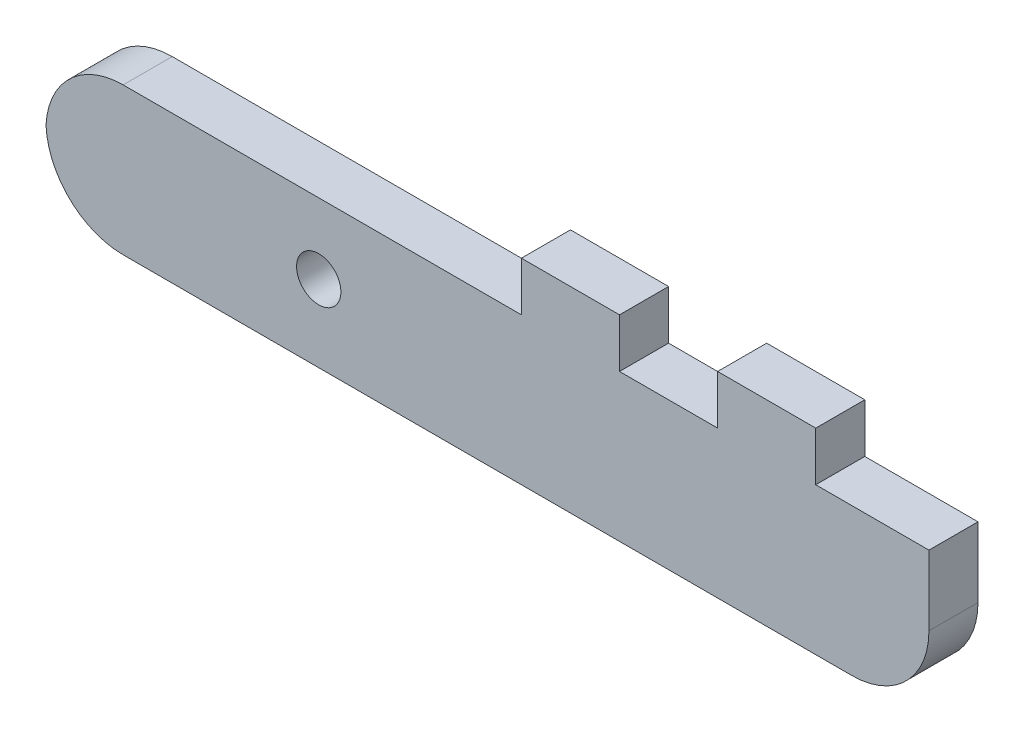
SolidWorks part; units mm, degrees
ref_plane "Front Plane" through (0, 0, 0) normal (0, 0, 1) x (1, 0, 0)
ref_plane "Top Plane" through (0, 0, 0) normal (0, 1, 0) x (1, 0, 0)
ref_plane "Right Plane" through (0, 0, 0) normal (1, 0, 0) x (0, 0, -1)
sketch "Sketch1" plane through (0, 0, 0) normal (0, 0, 1) x (1, 0, 0)
  line L1 (26.2356, 15.475) -> (38.9356, 15.475)
  line L2 (26.2356, 15.475) -> (26.2356, 9.125)
  line L4 (38.9356, 15.475) -> (38.9356, 9.125)
  line L5 (51.6356, 15.475) -> (64.3356, 15.475)
  line L6 (51.6356, 15.475) -> (51.6356, 9.125)
  line L8 (64.3356, 15.475) -> (64.3356, 9.125)
  line L9 (78.9882, 9.125) -> (64.3356, 9.125)
  line L10 (78.9882, 9.125) -> (78.9882, -9.925)
  line L11 (78.9882, -9.925) -> (-35.3118, -9.925)
  line L12 (-35.3118, 9.125) -> (-35.3118, -9.925)
  line L13 (26.2356, 9.125) -> (-35.3118, 9.125)
  line L14 (51.6356, 9.125) -> (38.9356, 9.125)
  dimension "D1" = 19.05
  dimension "D2" = 114.3
extrude "Boss-Extrude1" add sketch "Sketch1" along normal blind 6.35
fillet "Fillet1" radius 10 3 edges at (78.9882, -9.925, 3.175) (-35.3118, 9.125, 3.175) (-35.3118, -9.925, 3.175)
sketch "Sketch2" plane through (0, 0, 6.35) normal (0, 0, 1) x (1, 0, 0)
  circle A0 centre (0, 0) radius 2.8702
extrude "Cut-Extrude1" cut sketch "Sketch2" against normal through all
